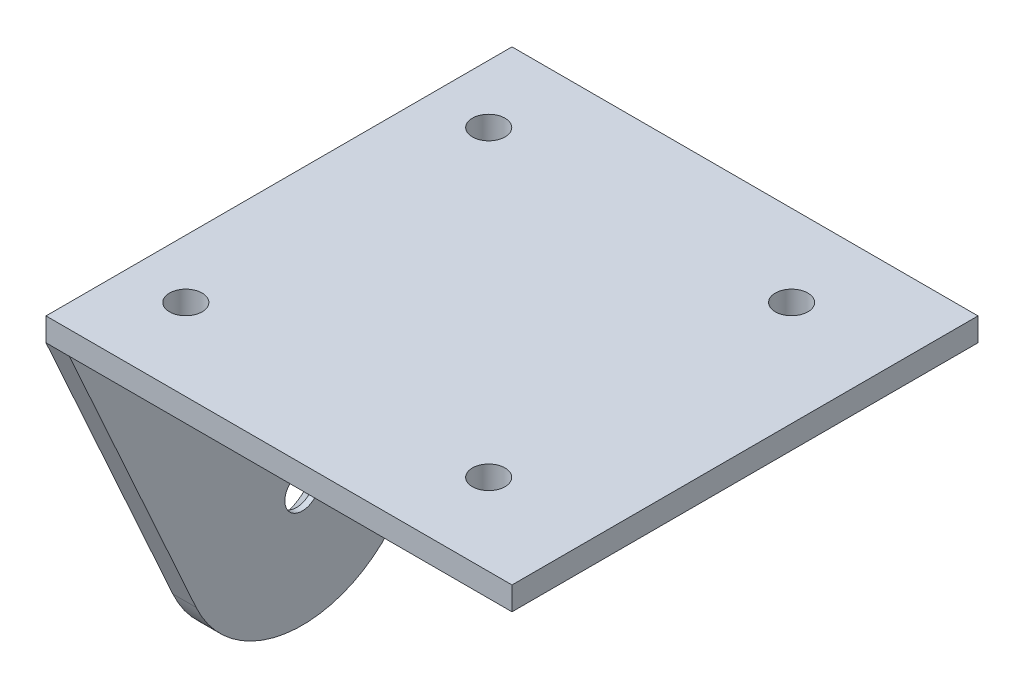
SolidWorks part; units mm, degrees
material "1060 Сплав"
ref_plane "Спереди" through (0, 0, 0) normal (0, 0, 1) x (1, 0, 0)
ref_plane "Сверху" through (0, 0, 0) normal (0, 1, 0) x (1, 0, 0)
ref_plane "Справа" through (0, 0, 0) normal (1, 0, 0) x (0, 0, -1)
sketch "Эскиз1" plane through (0, 0, 0) normal (0, 1, 0) x (1, 0, 0)
  line L1 (-9.5507, -16.723) -> (30.4493, -16.723)
  line L2 (-9.5507, -16.723) -> (-9.5507, 23.277)
  line L3 (-9.5507, 23.277) -> (30.4493, 23.277)
  line L4 (30.4493, -16.723) -> (30.4493, 23.277)
  line L5 (21.4493, -9.723) -> (-4.5507, -9.723) construction
  line L6 (21.4493, -9.723) -> (21.4493, 16.277) construction
  line L7 (21.4493, 16.277) -> (-4.5507, 16.277) construction
  line L8 (-4.5507, -9.723) -> (-4.5507, 16.277) construction
  line L10 (6.3748, 16.277) -> (6.3748, 23.277) construction
  line L11 (6.3748, -9.723) -> (6.3748, -16.723) construction
  circle A0 centre (-4.5507, 16.277) radius 1.4
  circle A1 centre (21.4493, 16.277) radius 1.4
  circle A2 centre (21.4493, -9.723) radius 1.4
  circle A3 centre (-4.5507, -9.723) radius 1.4
  dimension "D4" = 2.8
  dimension "D5" = 2.8
  dimension "D6" = 2.8
  dimension "D7" = 2.8
  dimension "D1" = 40
  dimension "D2" = 40
  dimension "D3" = 26
  dimension "D8" = 5
extrude "Основание уголка" add sketch "Эскиз1" along normal blind 2
sketch "Эскиз2" plane through (-9.5507, 0, 0) normal (-1, 0, 0) x (0, 0, 1)
  line L0 (-12.3914, -24.1144) -> (-23.277, 0)
  line L1 (-23.277, 0) -> (16.723, 0) construction
  line L2 (-23.277, 0) -> (16.723, 0)
  line L3 (16.723, 0) -> (5.8374, -24.1144)
  line L4 (-3.277, 0) -> (-3.277, -37.8522) construction
  circle A0 centre (-3.277, -20) radius 1.5
  arc A1 (-12.3914, -24.1144) -> (5.8374, -24.1144) centre (-3.277, -20) ccw
  dimension "D1" = 3
  dimension "D2" = 10
  dimension "D3" = 20
sketch "Эскиз3" [suppressed] plane through (-9.5507, 0, 0) normal (-1, 0, 0) x (0, 0, 1)
  line L0 (-3.277, 0) -> (-3.277, -42.9927) construction
  line L1 (-23.277, 0) -> (16.723, 0) construction
  line L2 (-12.6462, -28.4954) -> (-23.277, 0)
  line L3 (-23.277, 0) -> (16.723, 0)
  line L4 (16.723, 0) -> (6.0922, -28.4954)
  circle A0 centre (-3.277, -25) radius 1.5
  circle A1 centre (-3.277, -15) radius 1.5
  arc A2 (-12.6462, -28.4954) -> (6.0922, -28.4954) centre (-3.277, -25) ccw
  dimension "D1" = 10
  dimension "D2" = 3
  dimension "D3" = 3
  dimension "D4" = 10
  dimension "D5" = 20
extrude "Боковая с 2 отверстиями" [suppressed] add sketch "Эскиз3" against normal blind 2
extrude "Боковая с 1 отверстием" add sketch "Эскиз2" against normal blind 2
chamfer "Фаска 1 отвертие" distance 1.5 angle 45 1 edges at (-9.5507, -20, -1.777)
chamfer "Фаска 2 отверстия" [suppressed] distance 1.5 angle 45
sketch "Эскиз4" [suppressed] plane through (-7.5507, 0, 0) normal (1, 0, 0) x (0, 0, -1)
  line L0 (3.277, -3.5893) -> (3.277, -38.432) construction
  line L1 (0.277, -8.819) -> (6.277, -8.819)
  line L2 (6.277, -8.819) -> (8.2377, -24.3747)
  line L3 (0.277, -8.819) -> (-1.6838, -24.3747)
  arc A0 (-1.6838, -24.3747) -> (8.2377, -24.3747) centre (3.277, -25) ccw
  point P7 (3.277, -8.819)
  dimension "D1" = 5
  dimension "D2" = 6
extrude "Рычаг" [suppressed] add sketch "Эскиз4" along normal blind 3 separate body
fillet "Скругление рычага" [suppressed] radius 0.5
ref_axis "Ось поворота" [suppressed] through (31.4759, -25, -3.277) along (-1, 0, 0)
sketch "Эскиз5" [suppressed] plane through (-7.5507, 0, 0) normal (1, 0, 0) x (0, 0, -1)
  line L0 (3.277, -25) -> (3.277, -22.5) construction
  line L1 (3.7111, -22.538) -> (3.277, -25) construction
  circle A0 centre (3.277, -25) radius 2.5 construction
  arc A1 (3.277, -22.5) -> (3.7111, -22.538) centre (3.4834, -22.6411) cw
  arc A2 (3.7111, -22.538) -> (4.132, -22.6508) centre (3.8899, -22.7128) cw
  arc A3 (4.132, -22.6508) -> (4.527, -22.8349) centre (4.2777, -22.8539) cw
  arc A4 (4.527, -22.8349) -> (4.884, -23.0849) centre (4.6352, -23.0603) cw
  arc A5 (4.884, -23.0849) -> (5.1921, -23.393) centre (4.9514, -23.3256) cw
  arc A6 (5.1921, -23.393) -> (5.4421, -23.75) centre (5.2167, -23.6418) cw
  arc A7 (5.4421, -23.75) -> (5.6262, -24.1449) centre (5.4231, -23.9993) cw
  arc A8 (5.6262, -24.1449) -> (5.739, -24.5659) centre (5.5642, -24.3871) cw
  arc A9 (5.739, -24.5659) -> (5.777, -25) centre (5.6359, -24.7936) cw
  arc A10 (5.777, -25) -> (5.739, -25.4341) centre (5.6359, -25.2064) cw
  arc A11 (5.739, -25.4341) -> (5.6262, -25.8551) centre (5.5642, -25.6129) cw
  arc A12 (5.6262, -25.8551) -> (5.4421, -26.25) centre (5.4231, -26.0007) cw
  arc A13 (5.4421, -26.25) -> (5.1921, -26.607) centre (5.2167, -26.3582) cw
  arc A14 (5.1921, -26.607) -> (4.884, -26.9151) centre (4.9514, -26.6744) cw
  arc A15 (4.884, -26.9151) -> (4.527, -27.1651) centre (4.6352, -26.9397) cw
  arc A16 (4.527, -27.1651) -> (4.132, -27.3492) centre (4.2777, -27.1461) cw
  arc A17 (4.132, -27.3492) -> (3.7111, -27.462) centre (3.8899, -27.2872) cw
  arc A18 (3.7111, -27.462) -> (3.277, -27.5) centre (3.4834, -27.3589) cw
  arc A19 (3.277, -27.5) -> (2.8429, -27.462) centre (3.0706, -27.3589) cw
  arc A20 (2.8429, -27.462) -> (2.4219, -27.3492) centre (2.6641, -27.2872) cw
  arc A21 (2.4219, -27.3492) -> (2.027, -27.1651) centre (2.2763, -27.1461) cw
  arc A22 (2.027, -27.1651) -> (1.67, -26.9151) centre (1.9188, -26.9397) cw
  arc A23 (1.67, -26.9151) -> (1.3619, -26.607) centre (1.6026, -26.6744) cw
  arc A24 (1.3619, -26.607) -> (1.1119, -26.25) centre (1.3373, -26.3582) cw
  arc A25 (1.1119, -26.25) -> (0.9278, -25.8551) centre (1.1309, -26.0007) cw
  arc A26 (0.9278, -25.8551) -> (0.815, -25.4341) centre (0.9898, -25.6129) cw
  arc A27 (0.815, -25.4341) -> (0.777, -25) centre (0.9181, -25.2064) cw
  arc A28 (0.777, -25) -> (0.815, -24.5659) centre (0.9181, -24.7936) cw
  arc A29 (0.815, -24.5659) -> (0.9278, -24.1449) centre (0.9898, -24.3871) cw
  arc A30 (0.9278, -24.1449) -> (1.1119, -23.75) centre (1.1309, -23.9993) cw
  arc A31 (1.1119, -23.75) -> (1.3619, -23.393) centre (1.3373, -23.6418) cw
  arc A32 (1.3619, -23.393) -> (1.67, -23.0849) centre (1.6026, -23.3256) cw
  arc A33 (1.67, -23.0849) -> (2.027, -22.8349) centre (1.9188, -23.0603) cw
  arc A34 (2.027, -22.8349) -> (2.4219, -22.6508) centre (2.2763, -22.8539) cw
  arc A35 (2.4219, -22.6508) -> (2.8429, -22.538) centre (2.6641, -22.7128) cw
  arc A36 (2.8429, -22.538) -> (3.277, -22.5) centre (3.0706, -22.6411) cw
  point P114 (3.277, -25)
  dimension "D1" = 5
  dimension "D3" = 0.25
  dimension "D2" = 10
  dimension "D4" = 36
extrude "Серво-вал" [suppressed] add sketch "Эскиз5" along normal blind 4 separate body
ref_axis "Ось поворота без рычага" through (35.9866, -20, -3.277) along (-1, 0, 0)
ref_axis "Ось2" through (21.4493, 6.864, 9.723) along (0, -1, 0)
ref_axis "Ось3" through (-4.5507, 5.7973, 9.723) along (0, -1, 0)
ref_axis "Ось4" through (-4.5507, 5.35, -16.277) along (0, -1, 0)
ref_axis "Ось5" through (21.4493, 6.3269, -16.277) along (0, -1, 0)
ref_axis "Ось6" [suppressed] through (23.4493, 5.567, 9.723) along (0, -1, 0)
ref_axis "Ось7" [suppressed] through (23.4493, 6.3757, -16.277) along (0, -1, 0)
ref_axis "Ось8" [suppressed] through (-2.5507, 5.0347, -16.277) along (0, -1, 0)
ref_axis "Ось9" [suppressed] through (-2.5507, 5.4229, 9.723) along (0, -1, 0)
